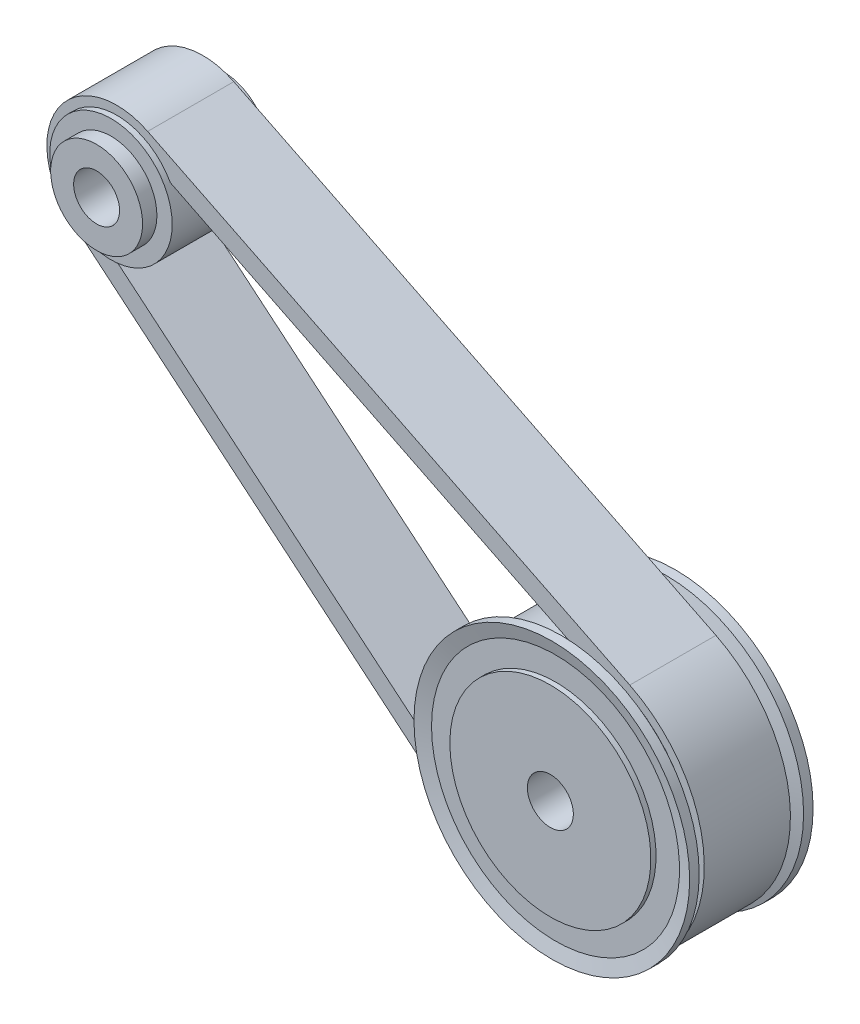
SolidWorks part; units mm, degrees
ref_plane "前视基准面" through (0, 0, 0) normal (0, 0, 1) x (1, 0, 0)
ref_plane "上视基准面" through (0, 0, 0) normal (0, 1, 0) x (1, 0, 0)
ref_plane "右视基准面" through (0, 0, 0) normal (1, 0, 0) x (0, 0, -1)
sketch "草图1" plane through (0, 0, 0) normal (0, 1, 0) x (1, 0, 0)
  line L0 (4, 0) -> (17.5, 0)
  line L1 (17.5, 0) -> (17.5, 0.9)
  line L2 (17.5, 0.9) -> (21.5891, 0.9)
  line L3 (21.5891, 0.9) -> (24, 0.254)
  line L4 (24, 0.254) -> (24, 1.9104)
  line L5 (24, 1.9104) -> (21.8, 2.4999)
  line L6 (21.8, 2.4999) -> (21.8, 19.5001)
  line L7 (21.8, 19.5001) -> (24, 20.0896)
  line L8 (24, 20.0896) -> (24, 21.746)
  line L9 (24, 21.746) -> (21.5891, 21.1)
  line L10 (21.5891, 21.1) -> (17.5, 21.1)
  line L11 (17.5, 21.1) -> (17.5, 22)
  line L12 (17.5, 22) -> (4, 22)
  line L13 (4, 22) -> (4, 0)
  line L14 (0, -50) -> (0, 50) construction
revolve "旋转1" add sketch "草图1" angle 360 about L14 reverse direction yes
ref_plane "基准面4" through (0, 0, -11) normal (0, 0, 1) x (1, 0, 0)
sketch "草图2" plane through (0, 0, -11) normal (0, 0, 1) x (1, 0, 0)
  line L0 (-86.7975, 42.1691) -> (-14.9409, -17.879)
  line L1 (10.3295, 20.8852) -> (-73.6092, 62.3998)
  line L2 (-84.6109, 44.7858) -> (-12.7543, -15.2624)
  line L3 (8.8177, 17.8286) -> (-75.1209, 59.3432)
  arc A0 (-73.6092, 62.3998) -> (-86.7975, 42.1691) centre (-79, 51.5) ccw
  arc A1 (-14.9409, -17.879) -> (10.3295, 20.8852) centre (0, 0) ccw
  arc A2 (-75.1209, 59.3432) -> (-84.6109, 44.7858) centre (-79, 51.5) ccw
  arc A3 (-12.7543, -15.2624) -> (8.8177, 17.8286) centre (0, 0) ccw
extrude "凸台-拉伸1" add sketch "草图2" against normal blind 7.5 and the other way blind 7.5
ref_plane "基准面5" through (0, 51.5, 0) normal (0, 1, 0) x (1, 0, 0)
sketch "草图3" plane through (0, 51.5, 0) normal (0, 1, 0) x (1, 0, 0)
  line L0 (-89.66, 2.5) -> (-87, 2.5)
  line L1 (-87, 2.5) -> (-87, 0)
  line L2 (-87, 0) -> (-83, 0)
  line L3 (-83, 0) -> (-83, 22)
  line L4 (-83, 22) -> (-87, 22)
  line L5 (-87, 22) -> (-87, 19.5)
  line L6 (-87, 19.5) -> (-89.66, 19.5)
  line L7 (-89.66, 19.5) -> (-89.66, 2.5)
  line L8 (-79, 50) -> (-79, -50) construction
revolve "旋转2" add sketch "草图3" angle 360 about L8 reverse direction yes
ref_plane "to_motor XY" through (0, 0, 0) normal (0, 0, 1) x (1, 0, 0)
ref_plane "to_motor XZ" through (0, 0, 0) normal (0, -1, 0) x (-1, 0, 0)
ref_plane "to_motor YZ" through (0, 0, 0) normal (1, 0, 0) x (0, 0, -1)
ref_axis "to_motor X" through (-80.9, 0, 0) along (1, 0, 0)
ref_axis "to_motor Y" through (0, -50, 0) along (0, 1, 0)
ref_axis "to_motor Z" through (0, 0, 80.9) along (0, 0, -1)
sketch3d "to_motor"
  point P0 (0, 0, 0)
